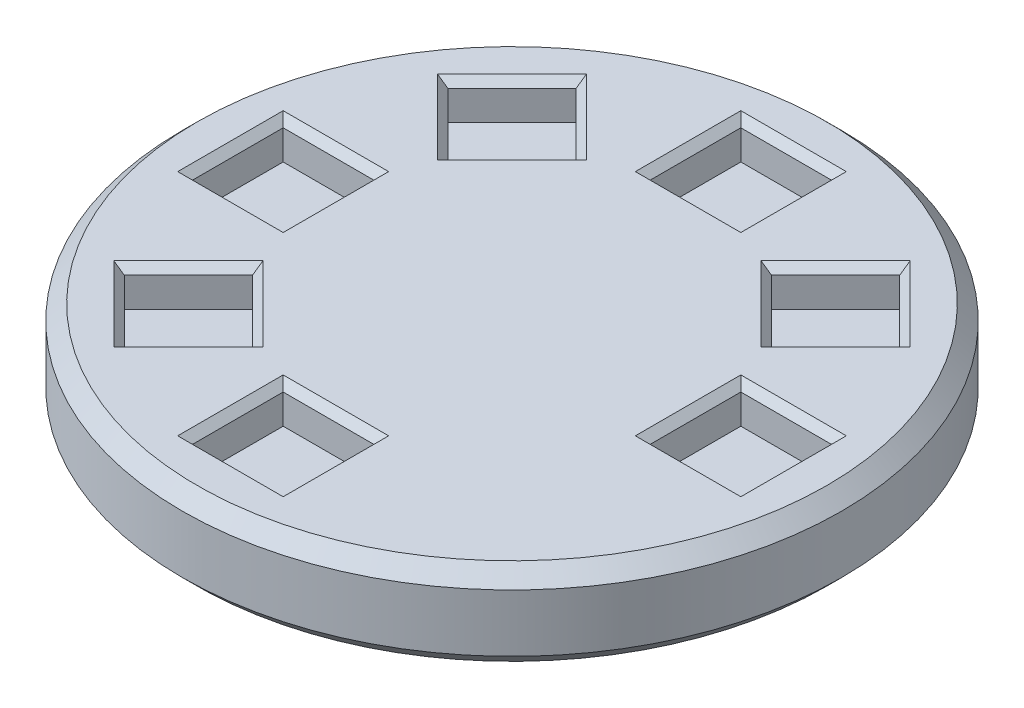
SolidWorks part; units mm, degrees
ref_plane "Front Plane" through (0, 0, 0) normal (0, 0, 1) x (1, 0, 0)
ref_plane "Top Plane" through (0, 0, 0) normal (0, 1, 0) x (1, 0, 0)
ref_plane "Right Plane" through (0, 0, 0) normal (1, 0, 0) x (0, 0, -1)
sketch "Sketch1" plane through (0, 0, 0) normal (0, 0, 1) x (1, 0, 0)
  line L0 (0, -2049.5716) -> (0, 100429.0072) construction
  line L1 (0, -32.3461) -> (9.2022, -32.3461)
  line L2 (9.2022, -32.3461) -> (9.2022, -11.7666)
  line L3 (9.2022, -11.7666) -> (44.5385, -11.7666)
  line L4 (44.5385, -11.7666) -> (44.5385, 0)
  line L5 (44.5385, 0) -> (0, 0)
  line L6 (0, 0) -> (0, -32.3461)
  point P8 (24.7863, 0)
  point P10 (30.9113, 0)
  point P13 (37.0363, 0)
  dimension "D1" = 12.25
  dimension "D2" = 6.125
revolve "Revolve1" add sketch "Sketch1" angle 360 about L0
sketch "Sketch3" plane through (0, 0, 0) normal (0, 1, 0) x (1, 0, 0)
  line L0 (9.2022, 0) -> (44.5385, 0) construction
  line L1 (24.7863, 6.125) -> (37.0363, 6.125)
  line L2 (24.7863, 6.125) -> (24.7863, -6.125)
  line L3 (24.7863, -6.125) -> (37.0363, -6.125)
  line L4 (37.0363, 6.125) -> (37.0363, -6.125)
  line L5 (0, 30.9113) -> (0, -30.9113) construction
  line L6 (-30.9113, 0) -> (30.9113, 0) construction
  line L7 (-21.8576, 21.8576) -> (21.8576, -21.8576) construction
  line L8 (-21.8576, -21.8576) -> (21.8576, 21.8576) construction
  circle A0 centre (0, 0) radius 30.9113 construction
  circle A1 centre (21.8576, -21.8576) radius 7.6687
  circle A2 centre (21.8576, -21.8576) radius 5.8584
  point P6 (30.9113, 0)
  point P9 (37.0363, 0)
  point P15 (30.9113, 6.125)
extrude "Cut-Extrude1" cut sketch "Sketch3" against normal blind 5 contours L4 L1 L2 L3 region at (30.9113, 0, 0)
chamfer "Chamfer1" distance 1 angle 45 4 edges at (37.0363, 0, 0) (30.9113, 0, 6.125) (24.7863, 0, 0) (30.9113, 0, -6.125)
pattern_circular "CirPattern1" count 8 over 360 about axis through (0, -2049.5716, 0) along (0, 1, 0) skipping 7 of "Cut-Extrude1", "Chamfer1"
ref_axis "Rotor Axis" through (0, -2049.5716, 0) along (0, 1, 0)
chamfer "Chamfer2" distance 2 angle 45 1 edges at (9.2022, -32.3461, 0)
chamfer "Chamfer3" distance 2 angle 45 2 edges at (44.5385, -11.7666, 0) (44.5385, 0, 0)
equation "\"D2@Sketch1\"=\"D1@Sketch1\"/2"
